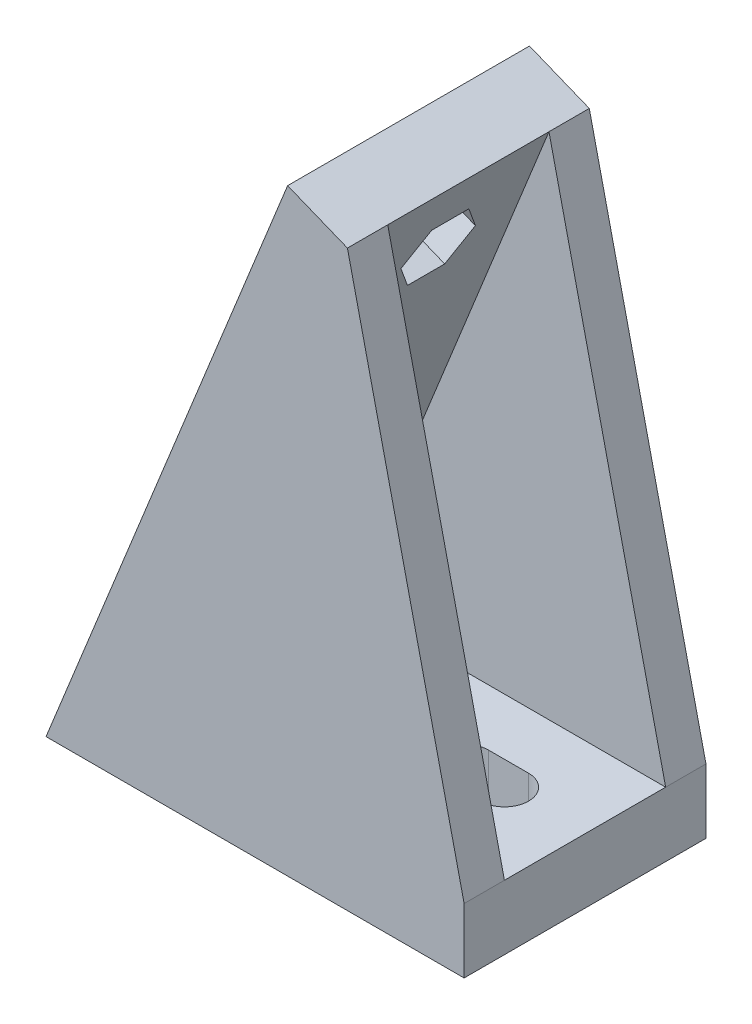
SolidWorks part; units mm, degrees
ref_plane "Front Plane" through (0, 0, 0) normal (0, 0, 1) x (1, 0, 0)
ref_plane "Top Plane" through (0, 0, 0) normal (0, 1, 0) x (1, 0, 0)
ref_plane "Right Plane" through (0, 0, 0) normal (1, 0, 0) x (0, 0, -1)
sketch "Sketch1" plane through (0, 0, 0) normal (0, 0, 1) x (1, 0, 0)
  line L0 (0, 0) -> (29.9685, 74.1747)
  line L4 (11.8605, 8) -> (37.386, 71.1779)
  line L5 (37.386, 71.1779) -> (29.9685, 74.1747)
  line L9 (0, 0) -> (51.8605, 0)
  line L13 (51.8605, 0) -> (51.8605, 8)
  line L15 (11.8605, 8) -> (51.8605, 8)
  point P3 (52.6481, 8.8251)
  point P4 (48.5798, 0)
  dimension "D1" = 68
  dimension "D2" = 8
  dimension "D3" = 8
  dimension "D4" = 80
  dimension "D6" = 40
extrude "Boss-Extrude1" add sketch "Sketch1" along normal mid plane 30
sketch "Sketch2" plane through (0.3799, 8, 0) normal (0, 1, 0) x (1, 0, 0)
  line L0 (41.4805, 0) -> (36.4805, 0) construction
  line L1 (41.4805, -3) -> (36.4805, -3)
  line L2 (41.4805, 3) -> (36.4805, 3)
  line L4 (51.4805, -15) -> (51.4805, 15) construction
  arc A0 (41.4805, -3) -> (41.4805, 3) centre (41.4805, 0) ccw
  arc A1 (36.4805, 3) -> (36.4805, -3) centre (36.4805, 0) ccw
  point P3 (38.9805, 0)
  dimension "D3" = 3
  dimension "D1" = 5
  dimension "D2" = 10
extrude "Cut-Extrude1" cut sketch "Sketch2" against normal through all
sketch "Sketch3" plane through (7.4175, -2.9969, 0) normal (0.9272, -0.3746, 0) x (0, 0, -1)
sketch "Sketch4" plane through (0, 0, 15) normal (0, 0, 1) x (1, 0, 0)
  line L0 (37.386, 71.1779) -> (51.8605, 8)
  line L1 (51.8605, 0) -> (51.8605, 8) construction
  line L2 (51.8605, 8) -> (11.8605, 8) construction
rib "Rib1" sketch "Sketch4" sketch "Sketch4" thickness 5 extrusion direction parallel to sketch draft on no parameters "D1"=5
mirror "Mirror1" about plane through (0, 0, 0) normal (0, 0, 1) of "Rib1"
sketch "Sketch6" plane through (7.4175, -2.9969, 0) normal (0.9272, -0.3746, 0) x (0, 0, -1)
  line L0 (-10, 80) -> (10, 80) construction
  point P0 (0, 70)
  point P2 (0, 25)
  point P9 (0, 80)
  dimension "D1" = 10
  dimension "D2" = 45
hole_wizard "M4 Clearance Hole1" positions "Sketch6" profile "Sketch7" hole size "M4" standard "ANSI Metric" end condition through all
sketch "Sketch7" plane through (33.6399, 61.906, 0) normal (0, 0, 1) x (0.3746, 0.9272, 0)
  line L0 (0, 0) -> (0, 35.7863)
  line L1 (0, 35.7863) -> (2.25, 35.7863)
  line L2 (2.25, 35.7863) -> (2.25, 0.025)
  line L3 (2.25, 0.025) -> (2.275, 0)
  line L5 (2.275, 0) -> (0, 0)
  line L6 (-2.25, 0.025) -> (-2.275, 0) construction
  line L11 (0, -6.35) -> (0, 107.95) construction
  dimension "Thru Hole Dia." = 4.5
  dimension "Thru Hole Depth" = 35.7863
  dimension "Near C'Sink Dia." = 4.55
  dimension "Near C'Sink Angle" = 90
sketch "Sketch8" plane through (7.4175, -2.9969, 0) normal (0.9272, -0.3746, 0) x (0, 0, -1)
  line L1 (4.6188, 70) -> (2.3094, 74)
  line L2 (2.3094, 74) -> (-2.3094, 74)
  line L3 (-2.3094, 74) -> (-4.6188, 70)
  line L4 (-4.6188, 70) -> (-2.3094, 66)
  line L5 (-2.3094, 66) -> (2.3094, 66)
  line L6 (2.3094, 66) -> (4.6188, 70)
  line L7 (4.6188, 25) -> (2.3094, 29)
  line L8 (2.3094, 29) -> (-2.3094, 29)
  line L9 (-2.3094, 29) -> (-4.6188, 25)
  line L10 (-4.6188, 25) -> (-2.3094, 21)
  line L11 (-2.3094, 21) -> (2.3094, 21)
  line L12 (2.3094, 21) -> (4.6188, 25)
  circle A0 centre (0, 70) radius 4 construction
  circle A1 centre (0, 25) radius 4 construction
  dimension "D1" = 8
  dimension "D2" = 8
extrude "Cut-Extrude2" cut sketch "Sketch8" against normal blind 3
fillet "Fillet1" radius 10 1 edges at (11.8605, 8, 0)
